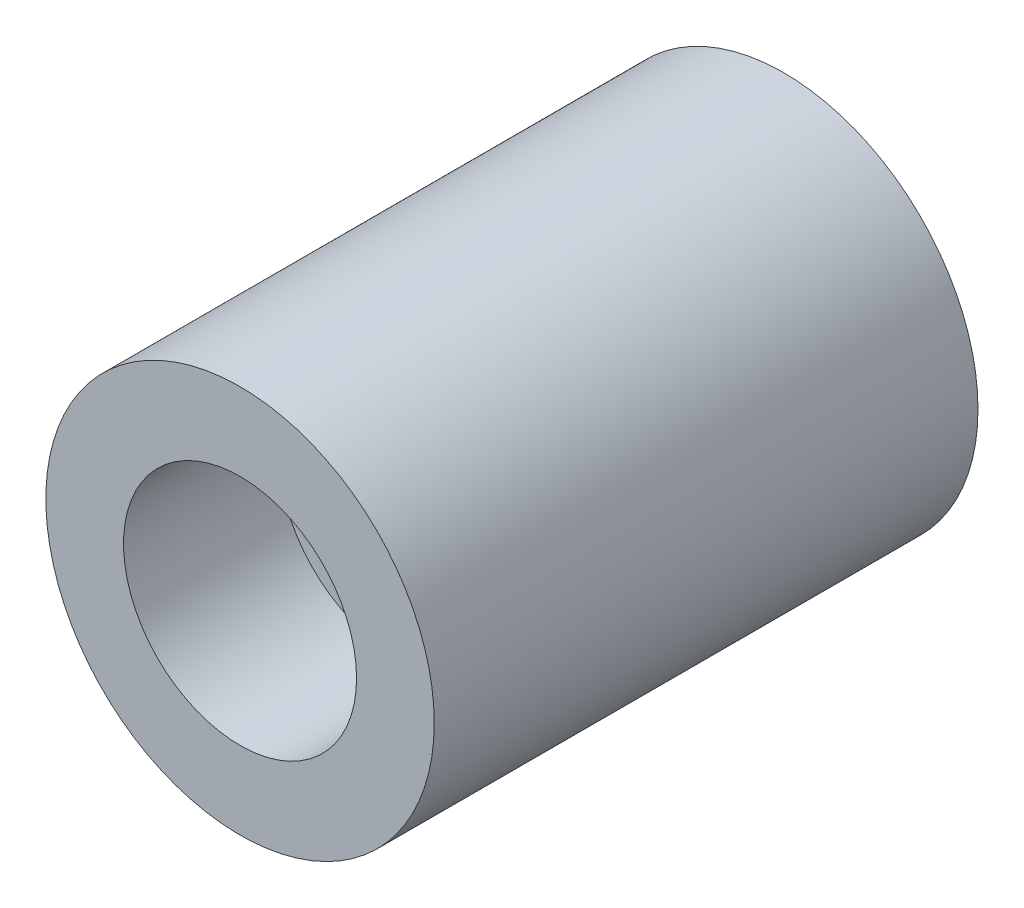
SolidWorks part; units mm, degrees
material "AISI 304"
ref_plane "Plan de face" through (0, 0, 0) normal (0, 0, 1) x (1, 0, 0)
ref_plane "Plan de dessus" through (0, 0, 0) normal (0, 1, 0) x (1, 0, 0)
ref_plane "Plan de droite" through (0, 0, 0) normal (1, 0, 0) x (0, 0, -1)
sketch "Esquisse1" plane through (0, 0, 0) normal (0, 0, 1) x (1, 0, 0)
  circle A0 centre (0, 0) radius 50
  circle A1 centre (0, 0) radius 30
  circle A2 centre (0, 0) radius 10
extrude "Boss.-Extru.1" add sketch "Esquisse1" along normal blind 20 contours A2 region at (0, 0, 0)
extrude "Boss.-Extru.2" add sketch "Esquisse1<3>" along normal blind 100 contours A1 A2 region at (-29.1515, 0, 0)
sketch "Esquisse1<3>" plane through (0, 0, 0) normal (0, 0, 1) x (1, 0, 0) same geometry as "Esquisse1"
extrude "Boss.-Extru.3" add sketch "Esquisse1<4>" along normal blind 140 contours A0 A1 region at (-48.5858, 0, 0)
sketch "Esquisse1<4>" plane through (0, 0, 0) normal (0, 0, 1) x (1, 0, 0) same geometry as "Esquisse1"
